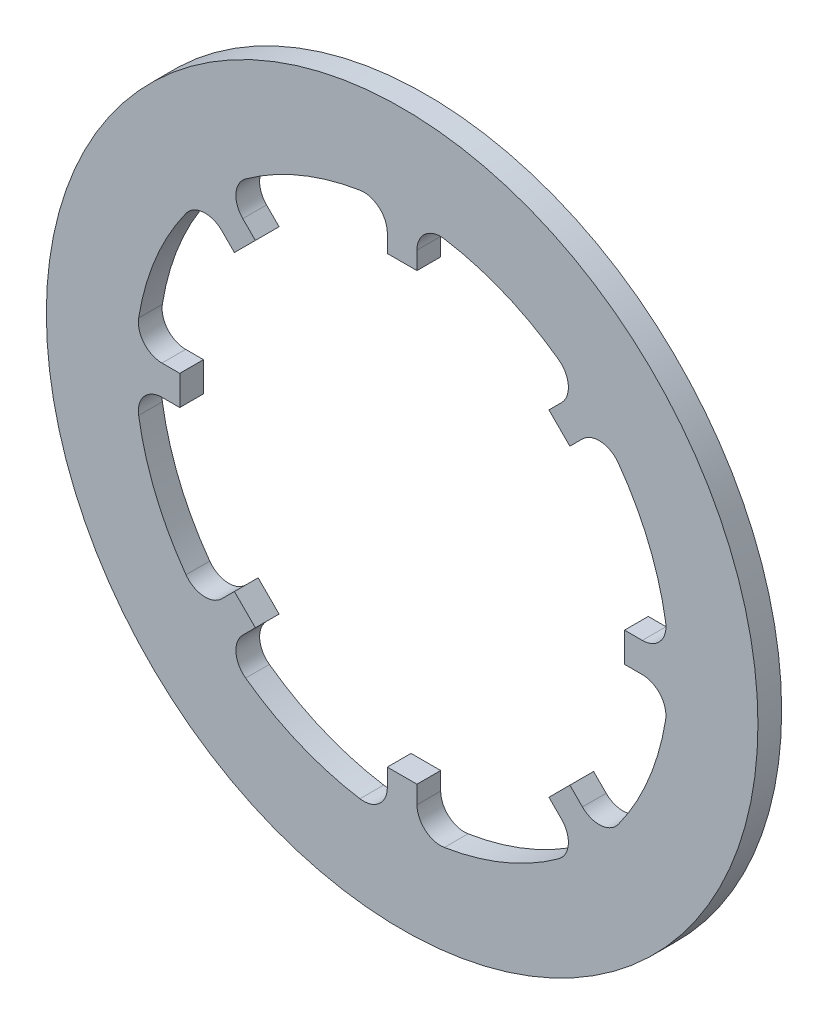
SolidWorks part; units mm, degrees
material "0.6010 (EN-GJL-100)"
ref_plane "Płaszczyzna przednia" through (0, 0, 0) normal (0, 0, 1) x (1, 0, 0)
ref_plane "Płaszczyzna górna" through (0, 0, 0) normal (0, 1, 0) x (1, 0, 0)
ref_plane "Płaszczyzna prawa" through (0, 0, 0) normal (1, 0, 0) x (0, 0, -1)
sketch "Szkic1" plane through (0, 0, 0) normal (0, 0, 1) x (1, 0, 0)
  circle A0 centre (0, 0) radius 120
  circle A1 centre (0, 0) radius 90
  dimension "D1" = 240
  dimension "D2" = 30
extrude "Dodanie-wyciągnięcie1" add sketch "Szkic1" along normal mid plane 8
sketch "Szkic2" plane through (0, 0, 0) normal (0, 0, 1) x (1, 0, 0)
  line L0 (5, 75) -> (-5, 75)
  line L1 (-5, 75) -> (-5, 81)
  line L2 (0, -4.4) -> (0, 4.4) construction
  line L3 (5, 75) -> (5, 81)
  arc A0 (-5, 81) -> (-14.2282, 88.8682) centre (-12.9684, 81) ccw
  circle A1 centre (0, 0) radius 90 construction
  arc A2 (14.2282, 88.8682) -> (-14.2282, 88.8682) centre (0, 0) ccw
  arc A3 (5, 81) -> (14.2282, 88.8682) centre (12.9684, 81) cw
  point P17 (0, 75)
  dimension "D4" = 180
  dimension "D2" = 6
  dimension "D3" = 75
  dimension "D1" = 5
extrude "Dodanie-wyciągnięcie2" add sketch "Szkic2" along normal up to surface (4 mm away) from surface up to face at (120, 0, 4) starting at face at (120, 0, -4)
pattern_circular "Szyk kołowy1" count 8 over 360 about axis through (0, 0, 4) along (0, 0, -1) of "Dodanie-wyciągnięcie2"
equation "\"D3@Szkic2\"=\"D4@Szkic2\"/2-15"
